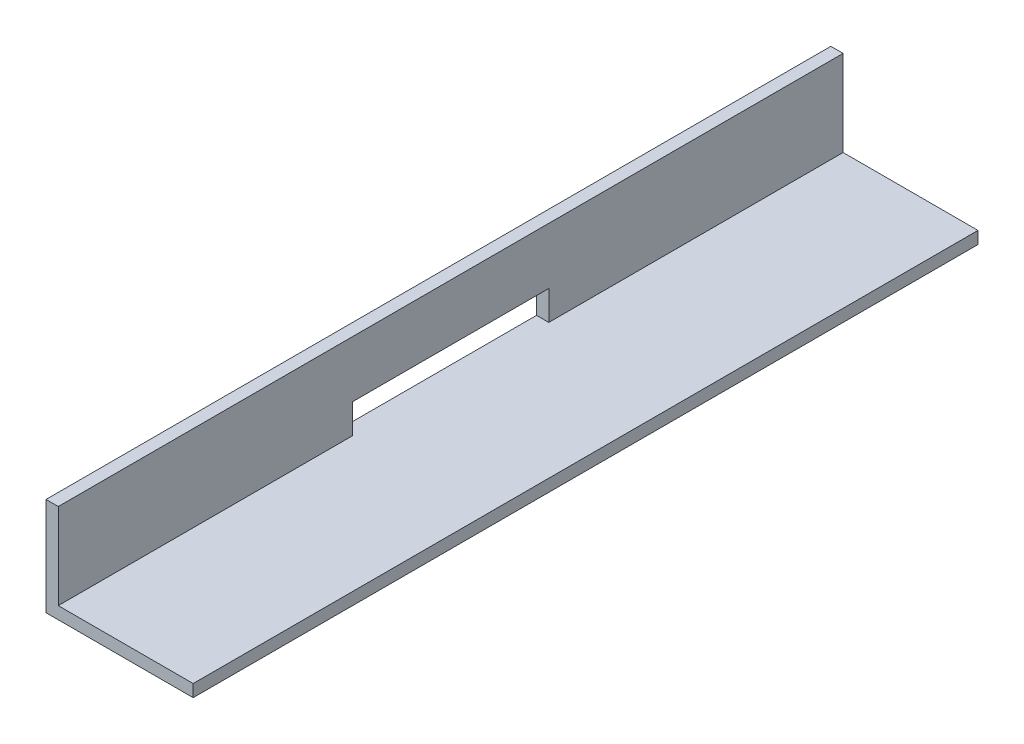
SolidWorks part; units mm, degrees
ref_plane "Front Plane" through (0, 0, 0) normal (0, 0, 1) x (1, 0, 0)
ref_plane "Top Plane" through (0, 0, 0) normal (0, 1, 0) x (1, 0, 0)
ref_plane "Right Plane" through (0, 0, 0) normal (1, 0, 0) x (0, 0, -1)
sketch "Sketch3" plane through (0, 0, 0) normal (0, 0, 1) x (1, 0, 0)
  line L0 (0, 0) -> (19.05, 0)
  line L1 (19.05, 0) -> (19.05, 1.5875)
  line L2 (19.05, 1.5875) -> (1.5875, 1.5875)
  line L3 (1.5875, 1.5875) -> (1.5875, 12.7)
  line L4 (1.5875, 12.7) -> (0, 12.7)
  line L5 (0, 12.7) -> (0, 0)
  dimension "D1" = 19.05
  dimension "D2" = 12.7
  dimension "D3" = 1.5875
  dimension "D4" = 1.5875
extrude "Boss-Extrude1" add sketch "Sketch3" along normal blind 101.6
sketch "Sketch4" plane through (1.5875, 0, 0) normal (1, 0, 0) x (0, 0, -1)
  line L0 (-101.6, 1.5875) -> (0, 1.5875) construction
  line L1 (-63.5, 1.5875) -> (-38.1, 1.5875)
  line L2 (-63.5, 1.5875) -> (-63.5, 5.3975)
  line L3 (-63.5, 5.3975) -> (-38.1, 5.3975)
  line L4 (-38.1, 1.5875) -> (-38.1, 5.3975)
  line L5 (-101.6, 12.7) -> (0, 12.7) construction
  point P8 (-50.8, 12.7)
  point P9 (-50.8, 5.3975)
  dimension "D1" = 25.4
  dimension "D2" = 3.81
extrude "Cut-Extrude1" cut sketch "Sketch4" against normal blind 2.54
